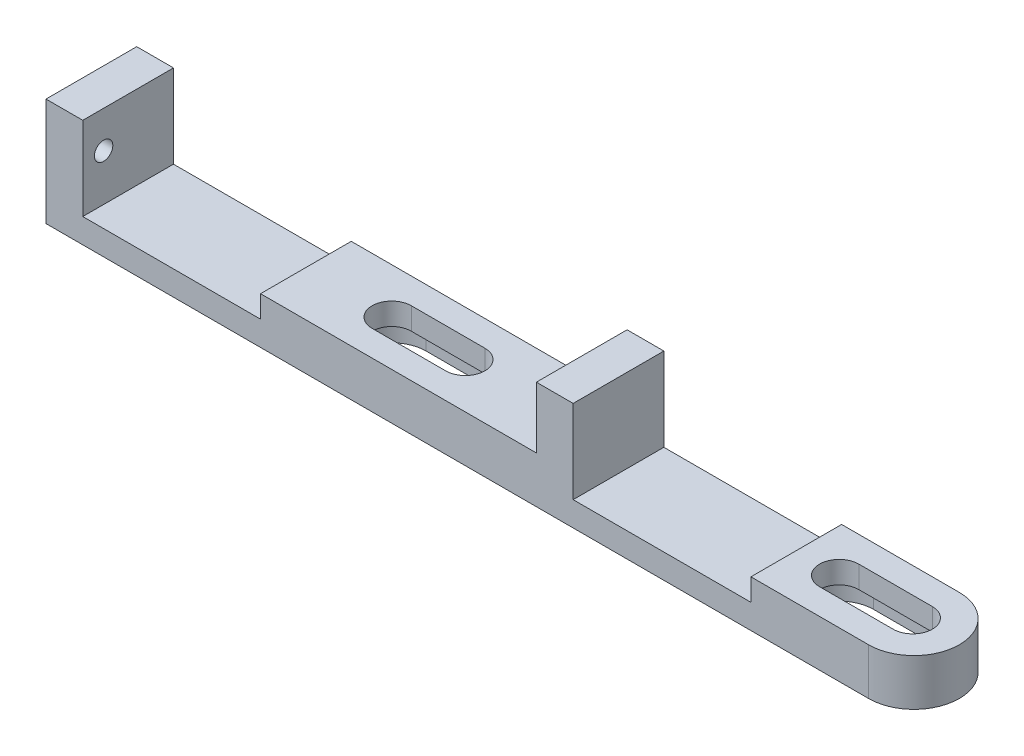
SolidWorks part; units mm, degrees
ref_plane "Front Plane" through (0, 0, 0) normal (0, 0, 1) x (1, 0, 0)
ref_plane "Top Plane" through (0, 0, 0) normal (0, 1, 0) x (1, 0, 0)
ref_plane "Right Plane" through (0, 0, 0) normal (1, 0, 0) x (0, 0, -1)
sketch "Sketch1" plane through (0, 0, 0) normal (0, 0, 1) x (1, 0, 0)
  line L0 (0, 0) -> (0, 8.8)
  line L1 (0, 0) -> (70.8, 0)
  line L8 (70.8, 0) -> (70.8, 3.8)
  line L10 (0, 8.8) -> (3, 8.8)
  line L11 (3, 8.8) -> (3, 2)
  line L20 (40, 3.8) -> (40, 8.8)
  line L21 (40, 8.8) -> (43, 8.8)
  line L22 (43, 8.8) -> (43, 2)
  line L23 (40, 3.8) -> (17.5, 3.8)
  line L24 (17.5, 3.8) -> (17.5, 2)
  line L25 (17.5, 2) -> (3, 2)
  line L26 (70.8, 3.8) -> (57.5, 3.8)
  line L27 (57.5, 3.8) -> (57.5, 2)
  line L28 (57.5, 2) -> (43, 2)
  dimension "D1" = 3
  dimension "D2" = 2
  dimension "D3" = 8.8
  dimension "D4" = 3.8
  dimension "D5" = 14.5
  dimension "D6" = 3
  dimension "D7" = 40
  dimension "D8" = 14.5
  dimension "D10" = 70.8
extrude "Boss-Extrude1" add sketch "Sketch1" along normal blind 7.4
sketch "Sketch3" plane through (0, 3.8, 0) normal (0, 1, 0) x (1, 0, 0)
  line L0 (30.5, -3.7) -> (24.5, -3.7) construction
  line L1 (30.5, -5.3) -> (24.5, -5.3)
  line L2 (30.5, -2.1) -> (24.5, -2.1)
  line L3 (67, -3.7) -> (61, -3.7) construction
  line L4 (67, -5.3) -> (61, -5.3)
  line L5 (67, -2.1) -> (61, -2.1)
  line L6 (40, -7.4) -> (40, 0) construction
  arc A0 (30.5, -5.3) -> (30.5, -2.1) centre (30.5, -3.7) ccw
  arc A1 (24.5, -2.1) -> (24.5, -5.3) centre (24.5, -3.7) ccw
  arc A2 (67, -5.3) -> (67, -2.1) centre (67, -3.7) ccw
  arc A3 (61, -2.1) -> (61, -5.3) centre (61, -3.7) ccw
  point P2 (27.5, -3.7)
  point P7 (64, -3.7)
  point P21 (40, -3.7)
  dimension "D2" = 1.6
  dimension "D1" = 6
  dimension "D3" = 12.5
  dimension "D4" = 36.5
extrude "Cut-Extrude1" cut sketch "Sketch3" against normal blind 10
sketch "Sketch4" plane through (0, 0, 0) normal (0, -1, 0) x (1, 0, 0)
  line L0 (24.5, 5.3) -> (30.5, 5.3) construction
  line L1 (30.5, 2.1) -> (24.5, 2.1) construction
  line L2 (24.5, 5.3) -> (30.5, 5.3)
  line L3 (30.5, 2.1) -> (24.5, 2.1)
  line L4 (61, 5.3) -> (67, 5.3) construction
  line L5 (67, 2.1) -> (61, 2.1) construction
  line L6 (61, 5.3) -> (67, 5.3)
  line L7 (67, 2.1) -> (61, 2.1)
  line L8 (24.5, 6.5) -> (30.5, 6.5)
  line L9 (30.5, 0.9) -> (24.5, 0.9)
  line L10 (61, 6.5) -> (67, 6.5)
  line L11 (67, 0.9) -> (61, 0.9)
  arc A0 (30.5, 2.1) -> (30.5, 5.3) centre (30.5, 3.7) ccw construction
  arc A1 (24.5, 5.3) -> (24.5, 2.1) centre (24.5, 3.7) ccw construction
  arc A2 (30.5, 2.1) -> (30.5, 5.3) centre (30.5, 3.7) ccw
  arc A3 (24.5, 5.3) -> (24.5, 2.1) centre (24.5, 3.7) ccw
  arc A4 (61, 5.3) -> (61, 2.1) centre (61, 3.7) ccw construction
  arc A5 (67, 2.1) -> (67, 5.3) centre (67, 3.7) ccw construction
  arc A6 (61, 5.3) -> (61, 2.1) centre (61, 3.7) ccw
  arc A7 (67, 2.1) -> (67, 5.3) centre (67, 3.7) ccw
  arc A8 (30.5, 0.9) -> (30.5, 6.5) centre (30.5, 3.7) ccw
  arc A9 (24.5, 6.5) -> (24.5, 0.9) centre (24.5, 3.7) ccw
  arc A10 (67, 0.9) -> (67, 6.5) centre (67, 3.7) ccw
  arc A11 (61, 6.5) -> (61, 0.9) centre (61, 3.7) ccw
  dimension "D1" = 1.2
  dimension "D2" = 1.2
extrude "Cut-Extrude2" cut sketch "Sketch4" against normal blind 2
sketch "Sketch5" plane through (0, 0, 0) normal (-1, 0, 0) x (0, 0, 1)
  line L0 (7.4, 8.8) -> (0, 8.8) construction
  line L2 (7.4, 8.8) -> (7.4, 0) construction
  circle A0 centre (5.7, 5.8) radius 0.75
  dimension "D1" = 1.5
  dimension "D2" = 3
  dimension "D3" = 1.7
extrude "Cut-Extrude3" cut sketch "Sketch5" against normal up to next
sketch "Sketch6" plane through (0, 0, 0) normal (0, -1, 0) x (1, 0, 0)
  line L0 (70.8, 0) -> (70.8, 7.4)
  line L1 (70.8, 7.4) -> (70.8, 0) construction
  line L2 (70.8, 7.4) -> (67.1, 7.4)
  line L3 (0, 7.4) -> (70.8, 7.4) construction
  line L4 (0, 0) -> (70.8, 0) construction
  line L5 (67.1, 0) -> (70.8, 0)
  arc A0 (67.1, 7.4) -> (67.1, 0) centre (67.1, 3.7) cw
  line M13 (0, 0) -> (70.8, 0)
  line M14 (70.8, 0) -> (70.8, 7.4)
  line M15 (70.8, 7.4) -> (0, 7.4)
extrude "Cut-Extrude4" cut sketch "Sketch6" against normal blind 10 contours A0 M14 M13 | A0 L0 M15 region at (69.9735, 0, 0.8265) region at (69.9735, 0, 6.5735)
